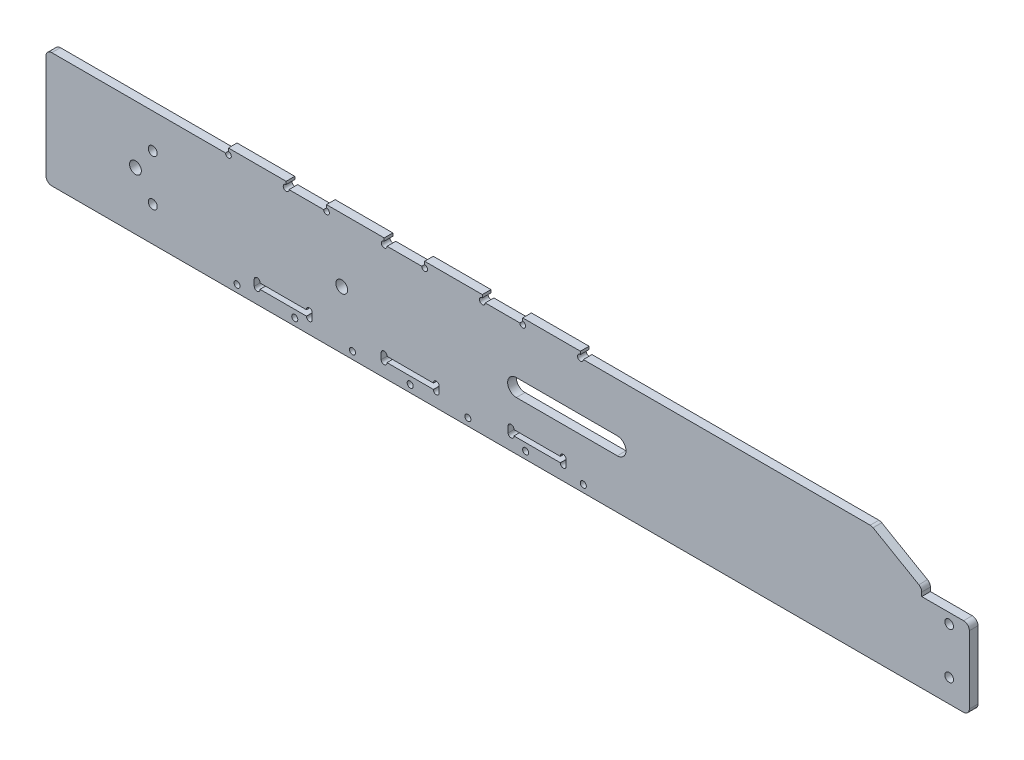
SolidWorks part; units mm, degrees
material "Thornel Mat VMA"
ref_plane "前视基准面" through (0, 0, 0) normal (0, 0, 1) x (1, 0, 0)
ref_plane "上视基准面" through (0, 0, 0) normal (0, 1, 0) x (1, 0, 0)
ref_plane "右视基准面" through (0, 0, 0) normal (1, 0, 0) x (0, 0, -1)
sketch "草图1" plane through (0, 0, 0) normal (0, 0, 1) x (1, 0, 0)
  line L1 (-184, -20) -> (184, -20)
  line L2 (-184, -20) -> (-184, 20)
  line L3 (-184, 20) -> (184, 20)
  line L4 (184, -20) -> (184, 20)
  line L5 (-184, -20) -> (184, 20) construction
  line L6 (-184, 20) -> (184, -20) construction
  point P0 (0, 0)
  dimension "D1" = 368
  dimension "D2" = 40
extrude "凸台-拉伸1" add sketch "草图1" along normal blind 3
sketch "草图2" plane through (0, 0, 0) normal (0, 0, 1) x (1, 0, 0)
  line L0 (-157.1827, 0) -> (155.6526, 0) construction
  line L1 (-184, -20) -> (-200, -20)
  line L2 (-184, -20) -> (-184, 7.5)
  line L3 (-184, 7.5) -> (-200, 7.5)
  line L4 (-200, -20) -> (-200, 7.5)
  line L5 (184, -20) -> (200, -20)
  line L6 (184, -20) -> (184, 7.5)
  line L7 (184, 7.5) -> (200, 7.5)
  line L8 (200, -20) -> (200, 7.5)
  dimension "D1" = 16
  dimension "D2" = 16
  dimension "D3" = 27.5
  dimension "D4" = 27.5
extrude "凸台-拉伸2" add sketch "草图2" along normal blind 3
sketch "草图3" plane through (0, 0, 3) normal (0, 0, 1) x (1, 0, 0)
  line L0 (-184, 20) -> (-184, 7.5) construction
  line L1 (-212.4147, 0) -> (176.0969, 0) construction
  line L2 (0, -57.7717) -> (0, 69.9209) construction
  line L3 (212.4147, 0) -> (-176.0969, 0) construction
  line L7 (-212.4147, 0) -> (176.0969, 0) construction
  line L8 (212.4147, 0) -> (-176.0969, 0) construction
  circle A0 centre (-193, -12) radius 1.5
  circle A1 centre (-193, 4) radius 1.5
  circle A4 centre (-149, 0) radius 4.5
  circle A7 centre (193, 4) radius 1.5
  circle A8 centre (193, -12) radius 1.5
  circle A9 centre (68, 0) radius 3
  dimension "D1" = 3
  dimension "D2" = 3
  dimension "D7" = 9
  dimension "D9" = 217
  dimension "D8" = 6
  dimension "D3" = 9
  dimension "D4" = 16
  dimension "D5" = 4
  dimension "D6" = 44
extrude "切除-拉伸1" cut sketch "草图3" against normal through all
sketch "草图6" plane through (0, 0, 3) normal (0, 0, 1) x (1, 0, 0)
  line L0 (-184, 7.5) -> (-200, 7.5) construction
  line L1 (-184, 20) -> (-183.5, 20)
  line L2 (-184, 20) -> (-184, 7.5)
  line L3 (-184, 7.5) -> (-183.5, 7.5)
  line L4 (-183.5, 20) -> (-183.5, 7.5)
  line L5 (184, 20) -> (183.5, 20)
  line L6 (184, 20) -> (184, 7.5)
  line L7 (184, 7.5) -> (183.5, 7.5)
  line L8 (183.5, 20) -> (183.5, 7.5)
  line L9 (200, 7.5) -> (184, 7.5) construction
  dimension "D1" = 0.5
  dimension "D2" = 0.5
  dimension "D3" = 0
  dimension "D4" = 0
extrude "切除-拉伸4" cut sketch "草图6" against normal blind 10
sketch "草图13" plane through (0, 0, 3) normal (0, 0, 1) x (1, 0, 0)
  line L0 (43, 0) -> (78, 0) construction
  line L1 (43, 3) -> (78, 3)
  line L2 (43, -3) -> (78, -3)
  arc A0 (43, 3) -> (43, -3) centre (43, 0) ccw
  arc A1 (78, -3) -> (78, 3) centre (78, 0) ccw
  circle A2 centre (68, 0) radius 3 construction
  point P3 (60.5, 0)
  dimension "D1" = 3
  dimension "D2" = 10
  dimension "D3" = 25
extrude "切除-拉伸10" cut sketch "草图13" against normal blind 10
sketch "草图14" plane through (0, 0, 3) normal (0, 0, 1) x (1, 0, 0)
  line L0 (-120, 20) -> (-120, -20)
  line L1 (183.5, 20) -> (-183.5, 20) construction
  line L2 (-200, -20) -> (200, -20) construction
  line L3 (-120, -20) -> (-200, -20)
  line L4 (-200, -20) -> (-200, 20)
  line L5 (-200, 20) -> (-120, 20)
  dimension "D1" = 80
extrude "切除-拉伸11" cut sketch "草图14" against normal blind 10
sketch "草图15" plane through (0, 0, 3) normal (0, 0, 1) x (1, 0, 0)
  line L0 (-62.2235, 0) -> (39.7809, 0) construction
  line L1 (-120, -20) -> (200, -20) construction
  line L2 (-120, -20) -> (-120, 20) construction
  line L3 (0, 0) -> (0, -20) construction
  line L4 (-17.5, 0) -> (-17.5, -4.9483) construction
  circle A0 centre (-89, 0) radius 2.05
  circle A1 centre (0, 0) radius 2.05 construction
  circle A4 centre (54, 0) radius 2.05
  circle A5 centre (-17.5, 0) radius 2.05
  dimension "D2" = 4.1
  dimension "D5" = 4.1
  dimension "D1" = 20
  dimension "D3" = 31
  dimension "D4" = 54
extrude "切除-拉伸12" cut sketch "草图15" against normal blind 10
sketch "草图16" plane through (0, 0, 0) normal (0, 0, -1) x (-1, 0, 0)
  circle A0 centre (-66.215, -17.5) radius 1.05
  circle A1 centre (-46.215, -17.5) radius 1.05
  circle A2 centre (-26.215, -17.5) radius 1.05
  circle A3 centre (-6.215, -17.5) radius 1.05
  circle A4 centre (13.785, -17.5) radius 1.05
  circle A5 centre (33.785, -17.5) radius 1.05
  circle A6 centre (53.785, -17.5) radius 1.05
  dimension "D1" = 2.1
extrude "切除-拉伸13" cut sketch "草图16" against normal blind 10
sketch "草图17" plane through (0, 0, 0) normal (0, 0, -1) x (-1, 0, 0)
  line L0 (-65.215, 20) -> (-65.215, 22)
  line L1 (-183.5, 20) -> (120, 20) construction
  line L2 (-65.215, 22) -> (-45.215, 22)
  line L3 (-45.215, 22) -> (-45.215, 20)
  line L4 (-45.215, 20) -> (-65.215, 20)
  line L5 (-75.215, 22) -> (-75.215, 20) construction
  line L6 (-21.215, 22) -> (-21.215, 7.5304) construction
  line L7 (-73.215, 22) -> (30.785, 22) construction
  line L9 (-11.215, 20) -> (-31.215, 20)
  line L10 (-31.215, 20) -> (-31.215, 22)
  line L11 (-31.215, 22) -> (-11.215, 22)
  line L12 (-11.215, 22) -> (-11.215, 20)
  line L13 (2.785, 20) -> (22.785, 20)
  line L14 (2.785, 22) -> (2.785, 20)
  line L15 (22.785, 22) -> (2.785, 22)
  line L16 (22.785, 20) -> (22.785, 22)
  line L17 (36.785, 20) -> (56.785, 20)
  line L18 (56.785, 22) -> (36.785, 22)
  line L19 (36.785, 22) -> (36.785, 20)
  line L20 (56.785, 20) -> (56.785, 22)
  dimension "D1" = 10
  dimension "D2" = 20
  dimension "D3" = 2
  dimension "D5" = 10
  dimension "D6" = 2
  dimension "D7" = 14
  dimension "D4" = 2
extrude "凸台-拉伸3" add sketch "草图17" against normal blind 3
sketch "草图18" plane through (0, 0, 0) normal (0, 0, -1) x (-1, 0, 0)
  line L0 (27.735, -12.95) -> (47.835, -12.95)
  line L1 (-60.265, -12.95) -> (-40.165, -12.95)
  line L2 (-60.265, -12.95) -> (-60.265, -15.05)
  line L3 (-60.265, -15.05) -> (-40.165, -15.05)
  line L4 (-40.165, -12.95) -> (-40.165, -15.05)
  line L5 (-60.265, -12.95) -> (-40.165, -15.05) construction
  line L6 (-60.265, -15.05) -> (-40.165, -12.95) construction
  line L7 (27.735, -15.05) -> (47.835, -15.05)
  line L8 (-40.165, -12.95) -> (-40.165, -15.05) construction
  line L9 (47.835, -12.95) -> (47.835, -15.05)
  line L13 (-16.265, -12.95) -> (3.835, -12.95)
  line L14 (-16.265, -15.05) -> (3.835, -15.05)
  line L15 (3.835, -12.95) -> (3.835, -15.05)
  line L16 (-16.265, -12.95) -> (-16.265, -15.05)
  line L17 (27.735, -12.95) -> (27.735, -15.05)
  point P0 (-50.215, -14)
  dimension "D2" = 44
extrude "切除-拉伸14" cut sketch "草图18" against normal through all
sketch "草图19" plane through (0, 0, 0) normal (0, 0, -1) x (-1, 0, 0)
  line L0 (-40.165, -12.95) -> (-60.265, -12.95) construction
  line L1 (-60.265, -15.05) -> (-40.165, -15.05) construction
  circle A0 centre (-59.265, -12.95) radius 1
  circle A1 centre (-59.265, -15.05) radius 1
  circle A2 centre (-41.165, -12.95) radius 1
  circle A3 centre (-41.165, -15.05) radius 1
  circle A4 centre (-15.265, -12.95) radius 1
  circle A5 centre (-15.265, -15.05) radius 1
  circle A6 centre (2.835, -12.95) radius 1
  circle A7 centre (2.835, -15.05) radius 1
  circle A8 centre (28.735, -12.95) radius 1
  circle A9 centre (28.735, -15.05) radius 1
  circle A10 centre (46.835, -12.95) radius 1
  circle A11 centre (46.835, -15.05) radius 1
  dimension "D1" = 2
  dimension "D3" = 44
  dimension "D2" = 3
extrude "切除-拉伸15" cut sketch "草图19" against normal blind 3
chamfer "倒角1" distance 10 angle 60 1 edges at (183.5, 20, 1.5) first distance on face at (183.5, 13.75, 1.5)
fillet "圆角2" radius 2 6 edges at (-120, 20, 1.5) (-120, -20, 1.5) (166.1795, 20, 1.5) (183.5, 10, 1.5) (200, 7.5, 1.5) (200, -20, 1.5)
sketch "草图22" plane through (0, 0, 0) normal (0, 0, -1) x (-1, 0, 0)
  line L0 (83, 20) -> (83, -12.95) construction
  line L1 (22.785, 20) -> (36.785, 20) construction
  line L2 (45.835, -12.95) -> (29.735, -12.95) construction
  circle A0 centre (89, 0) radius 2.05 construction
  circle A1 centre (83, 8) radius 1.55
  circle A2 centre (83, -8) radius 1.55
  dimension "D2" = 3.1
  dimension "D3" = 3.1
  dimension "D5" = 8
  dimension "D1" = 6
  dimension "D4" = 8
extrude "切除-拉伸17" cut sketch "草图22" against normal blind 10
sketch "草图24" plane through (0, 0, 0) normal (0, 0, -1) x (-1, 0, 0)
  line L0 (-58.265, -12.95) -> (-42.165, -12.95)
  line L1 (-58.265, -12.95) -> (-58.265, -13.05)
  line L2 (-42.165, -12.95) -> (-42.165, -13.05)
  line L3 (-58.265, -13.05) -> (-42.165, -13.05)
  line L4 (-58.265, -15.05) -> (-42.165, -15.05)
  line L5 (-58.265, -15.05) -> (-58.265, -14.95)
  line L6 (-42.165, -15.05) -> (-42.165, -14.95)
  line L7 (-58.265, -14.95) -> (-42.165, -14.95)
  line L8 (-14.265, -12.95) -> (1.835, -12.95)
  line L9 (-14.265, -12.95) -> (-14.265, -13.05)
  line L10 (1.835, -12.95) -> (1.835, -13.05)
  line L11 (-14.265, -13.05) -> (1.835, -13.05)
  line L12 (-14.265, -15.05) -> (1.835, -15.05)
  line L13 (-14.265, -15.05) -> (-14.265, -14.95)
  line L14 (1.835, -15.05) -> (1.835, -14.95)
  line L15 (-14.265, -14.95) -> (1.835, -14.95)
  line L16 (29.735, -12.95) -> (45.835, -12.95)
  line L17 (29.735, -12.95) -> (29.735, -13.05)
  line L18 (45.835, -12.95) -> (45.835, -13.05)
  line L19 (29.735, -13.05) -> (45.835, -13.05)
  line L20 (29.735, -15.05) -> (45.835, -15.05)
  line L21 (29.735, -15.05) -> (29.735, -14.95)
  line L22 (45.835, -15.05) -> (45.835, -14.95)
  line L23 (29.735, -14.95) -> (45.835, -14.95)
  line L24 (29.735, -15.05) -> (45.835, -15.05) construction
  arc A0 (29.735, -12.95) -> (27.735, -12.95) centre (28.735, -12.95) ccw construction
  arc A1 (27.735, -15.05) -> (29.735, -15.05) centre (28.735, -15.05) ccw construction
  dimension "D1" = 0.1
  dimension "D2" = 0.1
  dimension "D3" = 0.1
  dimension "D4" = 0.1
  dimension "D5" = 0.1
  dimension "D6" = 0.1
extrude "凸台-拉伸4" add sketch "草图24" against normal up to surface (3 mm away) up to face at (-84.55, 8, 3)
sketch "草图25" plane through (0, 0, 0) normal (0, 0, -1) x (-1, 0, 0)
  circle A0 centre (-65.215, 20) radius 1
  circle A1 centre (-45.215, 20) radius 1
  circle A2 centre (-31.215, 20) radius 1
  circle A3 centre (-11.215, 20) radius 1
  circle A4 centre (2.785, 20) radius 1
  circle A5 centre (22.785, 20) radius 1
  circle A6 centre (36.785, 20) radius 1
  circle A7 centre (56.785, 20) radius 1
  dimension "D1" = 2
  dimension "D2" = 2
  dimension "D3" = 2
  dimension "D4" = 2
  dimension "D5" = 2
  dimension "D6" = 2
  dimension "D7" = 2
  dimension "D8" = 2
extrude "切除-拉伸18" cut sketch "草图25" against normal blind 10
